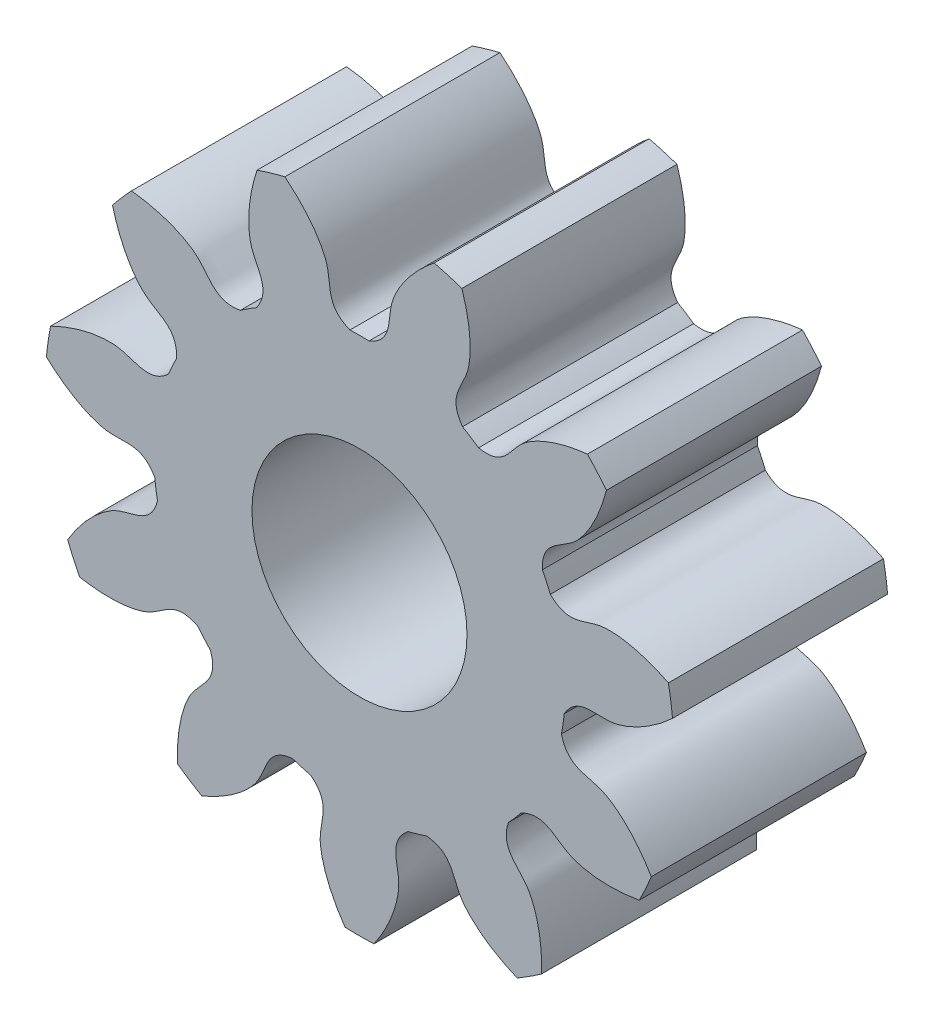
SolidWorks part; units mm, degrees
ref_plane "前视基准面" through (0, 0, 0) normal (0, 0, 1) x (1, 0, 0)
ref_plane "上视基准面" through (0, 0, 0) normal (0, 1, 0) x (1, 0, 0)
ref_plane "右视基准面" through (0, 0, 0) normal (1, 0, 0) x (0, 0, -1)
other "Configuration Table"
sketch "草图1" plane through (0, 0, 0) normal (0, 0, 1) x (1, 0, 0)
  circle A0 centre (0, 0) radius 2.925
extrude "凸台-拉伸1" add sketch "草图1" along normal blind 2
ref_axis "基准轴1" through (0, 0, 2) along (0, 0, -1)
sketch "草图2" plane through (0, 0, 0) normal (0, 0, 1) x (1, 0, 0)
  line L0 (0, 0) -> (0, 2.925) construction
  circle A0 centre (0, 0) radius 2.925 construction
  arc A1 (0.0885, 1.9104) -> (-0.0885, 1.9104) centre (0, 0) ccw
  arc A2 (1.6426, 3.2805) -> (-1.6426, 3.2805) centre (0, 0) ccw
  spline S0 degree 3 poles (0.0885, 1.9104) (0.3157, 2.001) (0.2586, 2.1861) (0.3071, 2.3434) (0.3099, 2.3518) (0.3131, 2.361) (0.3169, 2.371) (0.3212, 2.3818) (0.326, 2.3934) (0.3315, 2.4057) (0.3376, 2.4188) (0.3444, 2.4325) (0.3519, 2.447) (0.3602, 2.4621) (0.3692, 2.4779) (0.3789, 2.4942) (0.3895, 2.5112) (0.401, 2.5287) (0.4133, 2.5468) (0.4265, 2.5654) (0.4407, 2.5844) (0.4558, 2.6039) (0.4718, 2.6238) (0.4889, 2.6441) (0.5069, 2.6648) (0.526, 2.6858) (0.5462, 2.707) (0.5674, 2.7286) (0.5898, 2.7503) (0.6132, 2.7722) (0.6378, 2.7943) (0.6635, 2.8165) (0.6903, 2.8388) (0.7183, 2.8611) (0.7475, 2.8834) (0.7779, 2.9057) (0.8095, 2.9279) (0.8423, 2.9499) (0.8764, 2.9718) (0.9116, 2.9936) (0.9481, 3.015) (0.9858, 3.0363) (1.0247, 3.0571) (1.0649, 3.0777) (1.1063, 3.0978) (1.149, 3.1175) (1.1929, 3.1367) (1.238, 3.1554) (1.2844, 3.1735) (1.332, 3.191) (1.3808, 3.2078) (1.4308, 3.224) (1.482, 3.2394) (1.5525, 3.2591) (1.6063, 3.2723) (1.6426, 3.2805) knots 0 0 0 0 0.219011 0.222642 0.226699 0.231184 0.236096 0.241435 0.247201 0.253394 0.260015 0.267062 0.274537 0.282438 0.290767 0.299523 0.308706 0.318316 0.328354 0.338818 0.34971 0.361028 0.372774 0.384947 0.397547 0.410574 0.424029 0.43791 0.452219 0.466954 0.482117 0.497707 0.513724 0.530168 0.547039 0.564338 0.582063 0.600216 0.618795 0.637802 0.657236 0.677097 0.697385 0.718101 0.739243 0.760813 0.782809 0.805233 0.828084 0.851362 0.875067 0.8992 0.923759 0.948746 1 1 1 1
  spline S1 degree 3 poles (-0.0885, 1.9104) (-0.3157, 2.001) (-0.2586, 2.1861) (-0.3071, 2.3434) (-0.3099, 2.3518) (-0.3131, 2.361) (-0.3169, 2.371) (-0.3212, 2.3818) (-0.326, 2.3934) (-0.3315, 2.4057) (-0.3376, 2.4188) (-0.3444, 2.4325) (-0.3519, 2.447) (-0.3602, 2.4621) (-0.3692, 2.4779) (-0.3789, 2.4942) (-0.3895, 2.5112) (-0.401, 2.5287) (-0.4133, 2.5468) (-0.4265, 2.5654) (-0.4407, 2.5844) (-0.4558, 2.6039) (-0.4718, 2.6238) (-0.4889, 2.6441) (-0.5069, 2.6648) (-0.526, 2.6858) (-0.5462, 2.707) (-0.5674, 2.7286) (-0.5898, 2.7503) (-0.6132, 2.7722) (-0.6378, 2.7943) (-0.6635, 2.8165) (-0.6903, 2.8388) (-0.7183, 2.8611) (-0.7475, 2.8834) (-0.7779, 2.9057) (-0.8095, 2.9279) (-0.8423, 2.9499) (-0.8764, 2.9718) (-0.9116, 2.9936) (-0.9481, 3.015) (-0.9858, 3.0363) (-1.0247, 3.0571) (-1.0649, 3.0777) (-1.1063, 3.0978) (-1.149, 3.1175) (-1.1929, 3.1367) (-1.238, 3.1554) (-1.2844, 3.1735) (-1.332, 3.191) (-1.3808, 3.2078) (-1.4308, 3.224) (-1.482, 3.2394) (-1.5525, 3.2591) (-1.6063, 3.2723) (-1.6426, 3.2805) knots 0 0 0 0 0.219011 0.222642 0.226699 0.231184 0.236096 0.241435 0.247201 0.253394 0.260015 0.267062 0.274537 0.282438 0.290767 0.299523 0.308706 0.318316 0.328354 0.338818 0.34971 0.361028 0.372774 0.384947 0.397547 0.410574 0.424029 0.43791 0.452219 0.466954 0.482117 0.497707 0.513724 0.530168 0.547039 0.564338 0.582063 0.600216 0.618795 0.637802 0.657236 0.677097 0.697385 0.718101 0.739243 0.760813 0.782809 0.805233 0.828084 0.851362 0.875067 0.8992 0.923759 0.948746 1 1 1 1
extrude "切除-拉伸1" cut sketch "草图2" along normal through all
pattern_circular "阵列(圆周)1" count 11 every 32.727 about axis through (0, 0, 2) along (0, 0, -1) of "切除-拉伸1"
sketch "草图3" plane through (0, 0, 0) normal (0, 0, 1) x (1, 0, 0)
  circle A0 centre (0, 0) radius 2.475 construction
  dimension "Dn" = 4.95
sketch "草图4" plane through (0, 0, 2) normal (0, 0, 1) x (1, 0, 0)
  circle A0 centre (0, 0) radius 1
  dimension "D1" = 2
extrude "切除-拉伸2" cut sketch "草图4" against normal through all
